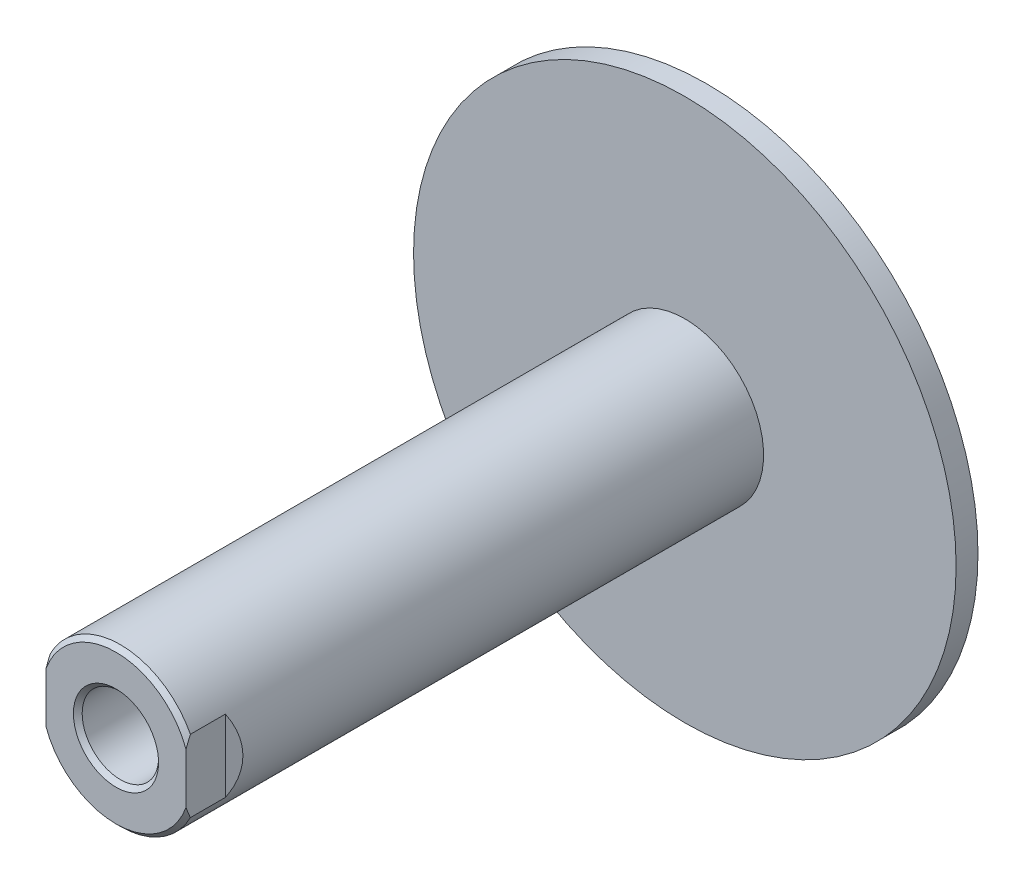
SolidWorks part; units mm, degrees
ref_plane "Plane1" through (0, 0, 0) normal (0, 0, 1) x (1, 0, 0)
ref_plane "Plane2" through (0, 0, 0) normal (0, 1, 0) x (1, 0, 0)
ref_plane "Plane3" through (0, 0, 0) normal (1, 0, 0) x (0, 0, -1)
sketch "Sketch1" plane through (0, 0, 0) normal (0, 0, 1) x (1, 0, 0)
  circle A0 centre (0, 0) radius 18
  dimension "D1" = 36
extrude "Base-Extrude" add sketch "Sketch1" along normal blind 5
sketch "Sketch6" plane through (0, 0, 0) normal (0, 0, -1) x (-1, 0, 0)
  circle A0 centre (0, 0) radius 17
  circle A1 centre (0, 0) radius 18
  circle A2 centre (0, 0) radius 18
  dimension "D1" = 0
  dimension "D2" = 1
extrude "Cut-Extrude1" cut sketch "Sketch6" against normal blind 1
sketch "Sketch7" plane through (0, 0, 5) normal (0, 0, 1) x (1, 0, 0)
  circle A1 centre (0, 0) radius 18
  circle A2 centre (0, 0) radius 18
  dimension "D1" = 0
extrude "Boss-Extrude1" add sketch "Sketch7" along normal up to surface (130 mm away)
chamfer "Chamfer1" distance 1 angle 45 1 edges at (-18, 0, 135)
sketch "Sketch2" plane through (0, 0, 135) normal (0, 0, 1) x (1, 0, 0)
  line L0 (0, 0) -> (0, 12.8) construction
  line L1 (16, 15) -> (16, -15)
  line L2 (-16, 15) -> (-16, -15)
  line L3 (16, -15) -> (26, -15)
  line L4 (-16, -15) -> (-26, -15)
  line L5 (26, -15) -> (26, 15)
  line L6 (-26, -15) -> (-26, 15)
  line L7 (26, 15) -> (16, 15)
  line L8 (-26, 15) -> (-16, 15)
  line L9 (0, 0) -> (26.4103, 0) construction
  dimension "D1" = 16
  dimension "D2" = 10
  dimension "D3" = 30
extrude "WrenchFlats" cut sketch "Sketch2" against normal blind 11
chamfer "WrenchFlatsChamfer" distance 2 angle 45 2 edges at (16, 0, 124) (-16, 0, 124)
sketch "Sketch3" plane through (0, 0, 135) normal (0, 0, 1) x (1, 0, 0)
  circle A0 centre (0, 0) radius 5
  dimension "D1" = 10
extrude "InternalThread" cut sketch "Sketch3" against normal blind 30
chamfer "InternalThreadChamfer" distance 1.2 angle 45 1 edges at (5, 0, 135)
sketch "Sketch4" plane through (0, 0, 135) normal (0, 0, 1) x (1, 0, 0)
  circle A2 centre (0, 0) radius 18
  dimension "D1" = 36
extrude "ExternalThread" [suppressed] add sketch "Sketch4" along normal blind 50
chamfer "ExternalThreadChamfer" [suppressed] distance 0.8 angle 45
ref_axis "Axis1" through (0, 0, 55) along (0, 0, -1)
sketch "Sketch5" plane through (0, 0, 0) normal (0, 0, -1) x (-1, 0, 0)
  circle A0 centre (0, 0) radius 62
  circle A1 centre (0, 0) radius 18 construction
  circle A2 centre (0, 0) radius 18
  dimension "D1" = 124
extrude "Piston" add sketch "Sketch5" against normal blind 5
ref_plane "L Starter" through (0, 0, 2.5) normal (0, 0, -1) x (-1, 0, 0)
hole_wizard "3/4-16 Tapped Hole1" positions "Sketch9" profile "Sketch8" tap size "3/4-16" standard "Ansi Inch"
sketch "Sketch9" plane through (0, 0, 135) normal (0, 0, 1) x (1, 0, 0)
  point P0 (0, 0)
sketch "Sketch8" plane through (0, 0, 135) normal (1, 0, 0) x (0, -1, 0)
  line L0 (0, 0) -> (0, 40.0063)
  line L1 (0, 40.0063) -> (8.7312, 34.76)
  line L2 (8.7312, 34.76) -> (8.7312, 0)
  line L5 (8.7312, 0) -> (0, 0)
  line L10 (0, 40.0063) -> (-8.7313, 34.76) construction
  line L11 (0, -6.35) -> (0, 107.95) construction
  dimension "Tap Drill Dia." = 17.4625
  dimension "Tap Drill Depth" = 34.76
  dimension "Drill Angle" = 118
chamfer "Chamfer2" distance 1 angle 45 1 edges at (8.7312, 0, 135)
